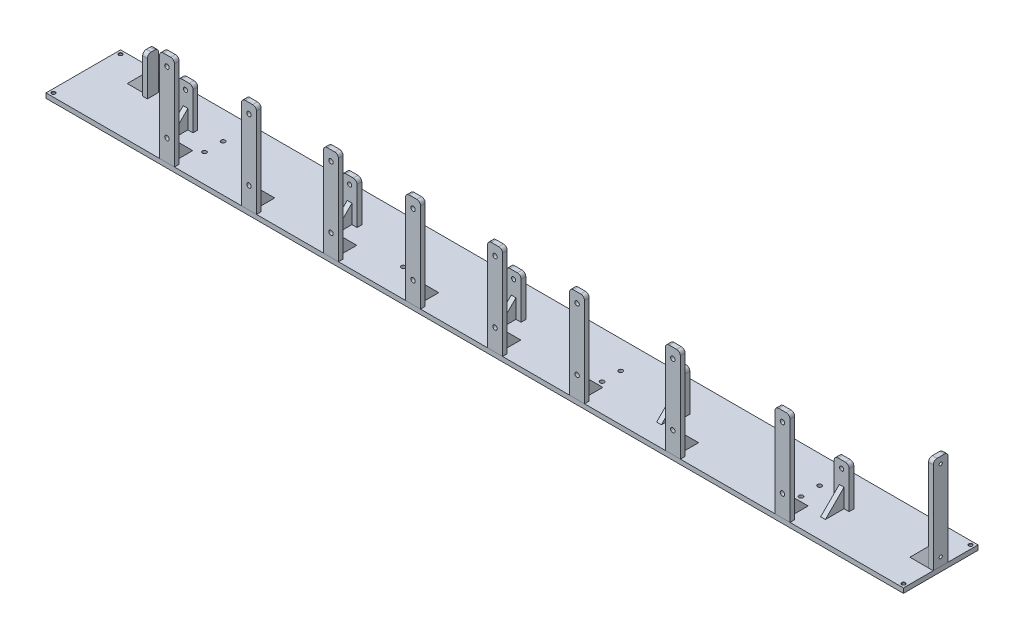
SolidWorks part; units mm, degrees
material "AISI 304"
ref_plane "Plan de face" through (0, 0, 0) normal (0, 0, 1) x (1, 0, 0)
ref_plane "Plan de dessus" through (0, 0, 0) normal (0, 1, 0) x (1, 0, 0)
ref_plane "Plan de droite" through (0, 0, 0) normal (1, 0, 0) x (0, 0, -1)
sketch "Esquisse1" plane through (0, 0, 0) normal (0, 1, 0) x (1, 0, 0)
  line L1 (-575, -50) -> (575, -50)
  line L2 (-575, -50) -> (-575, 50)
  line L3 (-575, 50) -> (575, 50)
  line L4 (575, -50) -> (575, 50)
  line L5 (-575, -50) -> (575, 50) construction
  line L6 (-575, 50) -> (575, -50) construction
  point P0 (0, 0)
  dimension "D1" = 1150
  dimension "D2" = 100
extrude "Boss.-Extru.1" add sketch "Esquisse1" along normal blind 6.35
hole_wizard "Dégagement M52" positions "Esquisse9" profile "Esquisse11" hole size "M5" standard "Ansi Metric" end condition up to next
sketch "Esquisse9" plane through (0, 6.35, 0) normal (0, 1, 0) x (1, 0, 0)
  line L2 (-400, 50) -> (-400, -50) construction
  line L3 (575, 50) -> (-575, 50) construction
  line L4 (-575, -50) -> (575, -50) construction
  line L6 (-133.3333, -50) -> (-133.3333, 50) construction
  line L8 (133.3333, 50) -> (133.3333, -50) construction
  line L10 (400, -50) -> (400, 50) construction
  line L12 (-400, 0) -> (-133.3333, 0) construction
  line L13 (-133.3333, 0) -> (133.3333, 0) construction
  line L14 (133.3333, 0) -> (400, 0) construction
  line L16 (-400, 12.5) -> (400, 12.5) construction
  line L18 (400, -12.5) -> (-400, -12.5) construction
  point P35 (-400, 12.5)
  point P36 (400, 12.5)
  point P39 (400, -12.5)
  point P40 (-400, -12.5)
  point P47 (-133.3333, -12.5)
  point P49 (-133.3333, 12.5)
  point P51 (133.3333, 12.5)
  point P53 (133.3333, -12.5)
  dimension "D1" = 25
  dimension "D3" = 800
sketch "Esquisse11" plane through (133.3333, 6.35, 12.5) normal (1, 0, 0) x (0, 0, 1)
  line L0 (0, 0) -> (0, 6.35)
  line L1 (0, 6.35) -> (2.75, 6.35)
  line L2 (2.75, 6.35) -> (2.75, 0)
  line L5 (2.75, 0) -> (0, 0)
  line L11 (0, -6.35) -> (0, 107.95) construction
  dimension "Diamètre du perçage jusqu'au prochain" = 5.5
  dimension "Profondeur du perçage jusqu'au prochain" = 6.35
ref_plane "Plan3" through (-500, 0, 0) normal (-1, 0, 0) x (0, 0, 1)
sketch "Esquisse5" plane through (-500, 0, 0) normal (-1, 0, 0) x (0, 0, 1)
  line L0 (-50, 6.35) -> (50, 6.35) construction
  line L1 (-26, 6.35) -> (-11, 6.35)
  line L2 (-26, 6.35) -> (-26, 53.35)
  line L3 (-21, 58.35) -> (-16, 58.35)
  line L4 (-11, 6.35) -> (-11, 53.35)
  line L7 (-18.5, 99.85) -> (-18.5, 6.35) construction
  line L8 (-50, 6.35) -> (-50, 0) construction
  arc A0 (-16, 58.35) -> (-11, 53.35) centre (-16, 53.35) cw
  arc A1 (-26, 53.35) -> (-21, 58.35) centre (-21, 53.35) cw
  dimension "D2" = 5
  dimension "D1" = 15
  dimension "D3" = 31.5
  dimension "D4" = 52
extrude "Boss.-Extru.4" add sketch "Esquisse5" along normal blind 6.35 separate body
ref_plane "Plan4" through (0, 0, -18.5) normal (0, 0, 1) x (1, 0, 0)
sketch "Esquisse6" plane through (0, 0, -18.5) normal (0, 0, 1) x (1, 0, 0)
  line L0 (-506.35, 31.35) -> (-531.35, 6.35)
  line L1 (-506.35, 6.35) -> (-506.35, 53.35) construction
  line L2 (-575, 6.35) -> (575, 6.35) construction
  line L3 (-531.35, 6.35) -> (-506.35, 6.35)
  line L4 (-506.35, 6.35) -> (-506.35, 31.35)
  dimension "D1" = 45
  dimension "D2" = 25
extrude "Boss.-Extru.5" add sketch "Esquisse6" along normal mid plane 6.35 separate body
ref_plane "Plan1" through (0, 0, -8.5) normal (0, 0, -1) x (-1, 0, 0)
sketch "Esquisse2" plane through (0, 0, -8.5) normal (0, 0, -1) x (-1, 0, 0)
  line L0 (-575, 6.35) -> (575, 6.35) construction
  line L1 (450, 6.35) -> (430, 6.35)
  line L2 (450, 6.35) -> (450, 56.35)
  line L3 (445, 61.35) -> (435, 61.35)
  line L4 (430, 6.35) -> (430, 56.35)
  arc A0 (435, 61.35) -> (430, 56.35) centre (435, 56.35) ccw
  arc A1 (450, 56.35) -> (445, 61.35) centre (445, 56.35) ccw
  point P10 (440, 61.35)
  dimension "D1" = 5
  dimension "D2" = 55
  dimension "D3" = 20
  dimension "D4" = 440
extrude "Boss.-Extru.2" add sketch "Esquisse2" against normal blind 6.35 separate body
ref_plane "Plan2" through (-440, 0, 0) normal (1, 0, 0) x (0, 0, -1)
sketch "Esquisse4" plane through (-440, 0, 0) normal (1, 0, 0) x (0, 0, -1)
  line L0 (2.15, 31.35) -> (-22.85, 6.35)
  line L1 (2.15, 56.35) -> (2.15, 6.35) construction
  line L2 (-50, 6.35) -> (50, 6.35) construction
  line L3 (2.15, 31.35) -> (2.15, 6.35)
  line L4 (2.15, 6.35) -> (-22.85, 6.35)
  dimension "D1" = 45
  dimension "D2" = 25
extrude "Boss.-Extru.3" add sketch "Esquisse4" along normal mid plane 6.35 separate body
hole_wizard "Dégagement M51" positions "Esquisse7" profile "Esquisse8" hole size "M5" standard "Ansi Metric" end condition through all
sketch "Esquisse7" plane through (0, 0, -2.15) normal (0, 0, 1) x (1, 0, 0)
  line L0 (-440, 61.35) -> (-440, 51.35) construction
  line L1 (-445, 61.35) -> (-435, 61.35) construction
  line L2 (-440, -3.4925) -> (-440, 3.4925) construction
  point P0 (-440, 51.35)
  dimension "D1" = 10
sketch "Esquisse8" plane through (-440, 51.35, -2.15) normal (1, 0, 0) x (0, -1, 0)
  line L0 (0, 0) -> (0, 47.85)
  line L1 (0, 47.85) -> (2.75, 47.85)
  line L2 (2.75, 47.85) -> (2.75, 0.025)
  line L3 (2.75, 0.025) -> (2.775, 0)
  line L5 (2.775, 0) -> (0, 0)
  line L6 (-2.75, 0.025) -> (-2.775, 0) construction
  line L11 (0, -6.35) -> (0, 107.95) construction
  dimension "Diamètre du perçage jusqu'au prochain" = 5.5
  dimension "Profondeur du perçage jusqu'au prochain" = 47.85
  dimension "Diamètre du fraisage entrant" = 5.55
  dimension "Angle du fraisage entrant" = 90
pattern_linear "Répétition linéaire1" count 5 spacing 220 along (1, 0, 0) of "Boss.-Extru.2", "Boss.-Extru.3", "Dégagement M51"
sketch "Esquisse12" plane through (0, 0, 50) normal (0, 0, 1) x (1, 0, 0)
  line L0 (-575, 6.35) -> (575, 6.35) construction
  line L1 (-422.75, 6.35) -> (-402.75, 6.35)
  line L2 (-422.75, 6.35) -> (-422.75, 126.35)
  line L3 (-417.75, 131.35) -> (-407.75, 131.35)
  line L4 (-402.75, 6.35) -> (-402.75, 126.35)
  line L5 (-312.75, 6.35) -> (-292.75, 6.35)
  line L6 (-312.75, 6.35) -> (-312.75, 126.35)
  line L7 (-307.75, 131.35) -> (-297.75, 131.35)
  line L8 (-292.75, 6.35) -> (-292.75, 126.35)
  line L9 (-202.75, 6.35) -> (-182.75, 6.35)
  line L10 (-202.75, 6.35) -> (-202.75, 126.35)
  line L11 (-197.75, 131.35) -> (-187.75, 131.35)
  line L12 (-182.75, 6.35) -> (-182.75, 126.35)
  line L13 (-92.75, 6.35) -> (-72.75, 6.35)
  line L14 (-92.75, 6.35) -> (-92.75, 126.35)
  line L15 (-87.75, 131.35) -> (-77.75, 131.35)
  line L16 (-72.75, 6.35) -> (-72.75, 126.35)
  line L17 (17.25, 6.35) -> (37.25, 6.35)
  line L18 (17.25, 6.35) -> (17.25, 126.35)
  line L19 (22.25, 131.35) -> (32.25, 131.35)
  line L20 (37.25, 6.35) -> (37.25, 126.35)
  line L21 (127.25, 6.35) -> (147.25, 6.35)
  line L22 (127.25, 6.35) -> (127.25, 126.35)
  line L23 (132.25, 131.35) -> (142.25, 131.35)
  line L24 (147.25, 6.35) -> (147.25, 126.35)
  line L25 (255.75, 6.35) -> (275.75, 6.35)
  line L26 (255.75, 6.35) -> (255.75, 126.35)
  line L27 (260.75, 131.35) -> (270.75, 131.35)
  line L28 (275.75, 6.35) -> (275.75, 126.35)
  line L29 (402.75, 6.35) -> (422.75, 6.35)
  line L30 (402.75, 6.35) -> (402.75, 126.35)
  line L31 (407.75, 131.35) -> (417.75, 131.35)
  line L32 (422.75, 6.35) -> (422.75, 126.35)
  arc A0 (-407.75, 131.35) -> (-402.75, 126.35) centre (-407.75, 126.35) cw
  arc A1 (-422.75, 126.35) -> (-417.75, 131.35) centre (-417.75, 126.35) cw
  arc A2 (-297.75, 131.35) -> (-292.75, 126.35) centre (-297.75, 126.35) cw
  arc A3 (-312.75, 126.35) -> (-307.75, 131.35) centre (-307.75, 126.35) cw
  arc A4 (-187.75, 131.35) -> (-182.75, 126.35) centre (-187.75, 126.35) cw
  arc A5 (-202.75, 126.35) -> (-197.75, 131.35) centre (-197.75, 126.35) cw
  arc A6 (-77.75, 131.35) -> (-72.75, 126.35) centre (-77.75, 126.35) cw
  arc A7 (-92.75, 126.35) -> (-87.75, 131.35) centre (-87.75, 126.35) cw
  arc A8 (32.25, 131.35) -> (37.25, 126.35) centre (32.25, 126.35) cw
  arc A9 (17.25, 126.35) -> (22.25, 131.35) centre (22.25, 126.35) cw
  arc A10 (142.25, 131.35) -> (147.25, 126.35) centre (142.25, 126.35) cw
  arc A11 (127.25, 126.35) -> (132.25, 131.35) centre (132.25, 126.35) cw
  arc A12 (270.75, 131.35) -> (275.75, 126.35) centre (270.75, 126.35) cw
  arc A13 (255.75, 126.35) -> (260.75, 131.35) centre (260.75, 126.35) cw
  arc A14 (417.75, 131.35) -> (422.75, 126.35) centre (417.75, 126.35) cw
  arc A15 (402.75, 126.35) -> (407.75, 131.35) centre (407.75, 126.35) cw
  dimension "D1" = 5
  dimension "D5" = 110
  dimension "D6" = 128.5
  dimension "D7" = 147
  dimension "D8" = 20
  dimension "D9" = 125
  dimension "D10" = 422.75
  dimension "D2" = 6
  dimension "D3" = 2
  dimension "D4" = 2
extrude "Boss.-Extru.6" add sketch "Esquisse12" against normal blind 6.35 separate body
ref_plane "Plan5" through (-412.75, 0, 0) normal (-1, 0, 0) x (0, 0, 1)
sketch "Esquisse14" plane through (-412.75, 0, 0) normal (-1, 0, 0) x (0, 0, 1)
  line L0 (43.65, 31.35) -> (43.65, 6.35)
  line L1 (43.65, 126.35) -> (43.65, 6.35) construction
  line L2 (43.65, 6.35) -> (18.65, 6.35)
  line L3 (-50, 6.35) -> (50, 6.35) construction
  line L4 (18.65, 6.35) -> (43.65, 31.35)
  dimension "D1" = 45
  dimension "D2" = 25
extrude "Boss.-Extru.7" add sketch "Esquisse14" along normal mid plane 6.35 separate body
pattern_linear "Répétition linéaire2" count 6 spacing 110 along (1, 0, 0) of bodies 125
pattern_linear "Répétition linéaire3" count 2 spacing 128.5 along (1, 0, 0) of bodies 130
pattern_linear "Répétition linéaire4" count 2 spacing 147 along (1, 0, 0) of bodies 131
hole_wizard "Trou pour taraudage pour trou taraudé M7x1.01" positions "Esquisse17" profile "Esquisse18" hole size "M7x1.0" standard "Ansi Metric" end condition up to next
sketch "Esquisse17" plane through (0, 0, 50) normal (0, 0, 1) x (1, 0, 0)
  line L0 (-412.75, 6.35) -> (-412.75, 35) construction
  line L1 (-422.75, 6.35) -> (-402.75, 6.35) construction
  line L2 (-412.75, 35) -> (-412.75, 118) construction
  line L4 (-575, 0) -> (575, 0) construction
  point P0 (-412.75, 118)
  point P2 (-412.75, 35)
  point P19 (-302.75, 118)
  point P20 (-302.75, 35)
  point P21 (-192.75, 118)
  point P22 (-192.75, 35)
  point P23 (-82.75, 118)
  point P24 (-82.75, 35)
  point P25 (27.25, 118)
  point P26 (27.25, 35)
  point P27 (137.25, 118)
  point P28 (137.25, 35)
  point P34 (265.75, 118)
  point P35 (265.75, 35)
  point P41 (412.75, 118)
  point P42 (412.75, 35)
  dimension "D1" = 35
  dimension "D2" = 118
  dimension "D4" = 110
  dimension "D6" = 128.5
  dimension "D8" = 147
  dimension "D3" = 6
  dimension "D5" = 2
  dimension "D7" = 2
sketch "Esquisse18" plane through (-412.75, 118, 50) normal (1, 0, 0) x (0, -1, 0)
  line L0 (0, 0) -> (0, 6.351)
  line L1 (0, 6.351) -> (3, 6.351)
  line L2 (3, 6.351) -> (3, 0)
  line L5 (3, 0) -> (0, 0)
  line L11 (0, -6.35) -> (0, 107.95) construction
  dimension "Diamètre du perçage jusqu'au prochain" = 6
  dimension "Profondeur du perçage jusqu'au prochain" = 6.351
hole_wizard "Trou taraudé M5x0.81" positions "Esquisse15" profile "Esquisse16" tap size "M5x0.8" standard "Ansi Metric" end condition up to next
sketch "Esquisse15" plane through (0, 6.35, 0) normal (0, 1, 0) x (1, 0, 0)
  line L0 (575, -50) -> (575, 50) construction
  line L1 (-575, -50) -> (575, -50) construction
  point P0 (570, -45)
  dimension "D1" = 5
  dimension "D2" = 5
sketch "Esquisse16" plane through (570, 6.35, 45) normal (1, 0, 0) x (0, 0, 1)
  line L0 (0, 0) -> (0, 6.351)
  line L1 (0, 6.351) -> (2.1, 6.351)
  line L2 (2.1, 6.351) -> (2.1, 0.425)
  line L3 (2.1, 0.425) -> (2.525, 0)
  line L5 (2.525, 0) -> (0, 0)
  line L6 (-2.1, 0.425) -> (-2.525, 0) construction
  line L11 (0, -6.35) -> (0, 107.95) construction
  dimension "Diamètre du trou pour taraudage jusqu'au prochain" = 4.2
  dimension "Profondeur du trou pour taraudage jusqu'au prochain" = 6.351
  dimension "Diamètre du fraisage entrant" = 5.05
  dimension "Angle du fraisage entrant" = 90
cosmetic thread "Filetage de perçage1" parameters "D2"=5
mirror "Symétrie1" about plane through (0, 0, 0) normal (0, 0, 1) of "Trou taraudé M5x0.81"
cosmetic thread "Filetage de perçage2" parameters "D2"=5
mirror "Symétrie2" about plane through (0, 0, 0) normal (1, 0, 0) of "Trou taraudé M5x0.81", "Symétrie1"
cosmetic thread "Filetage de perçage3" parameters "D2"=5
cosmetic thread "Filetage de perçage4" parameters "D2"=5
sketch "Esquisse19" plane through (575, 0, 0) normal (1, 0, 0) x (0, 0, -1)
  line L0 (-10, 6.35) -> (10, 6.35)
  line L1 (-22.85, 6.35) -> (2.15, 6.35) construction
  line L2 (-50, 6.35) -> (50, 6.35) construction
  line L3 (10, 6.35) -> (10, 129.35)
  line L4 (5, 134.35) -> (-5, 134.35)
  line L5 (-10, 129.35) -> (-10, 6.35)
  line L6 (0, 0) -> (0, 6.35) construction
  arc A0 (10, 129.35) -> (5, 134.35) centre (5, 129.35) ccw
  arc A1 (-5, 134.35) -> (-10, 129.35) centre (-5, 129.35) ccw
  dimension "D2" = 5
  dimension "D1" = 20
  dimension "D3" = 128
extrude "Boss.-Extru.8" add sketch "Esquisse19" against normal blind 6.35 separate body
ref_plane "Plan6" through (0, 0, 0) normal (0, 0, 1) x (1, 0, 0)
sketch "Esquisse20" plane through (0, 0, 0) normal (0, 0, 1) x (1, 0, 0)
  line L0 (568.65, 31.35) -> (543.65, 6.35)
  line L1 (568.65, 129.35) -> (568.65, 6.35) construction
  line L2 (-575, 6.35) -> (575, 6.35) construction
  line L3 (543.65, 6.35) -> (568.65, 6.35)
  line L4 (568.65, 6.35) -> (568.65, 31.35)
  dimension "D1" = 45
  dimension "D2" = 25
extrude "Boss.-Extru.9" add sketch "Esquisse20" against normal blind 6.35 from surface separate body starting at face at (571.825, 67.85, 10)
extrude "Boss.-Extru.10" add sketch "Esquisse20<2>" along normal blind 6.35 from surface separate body starting at face at (571.825, 67.85, -10)
sketch "Esquisse20<2>" plane through (0, 0, 0) normal (0, 0, 1) x (1, 0, 0) same geometry as "Esquisse20"
hole_wizard "Trou taraudé M5x0.82" positions "Esquisse21" profile "Esquisse22" tap size "M5x0.8" standard "Ansi Metric" end condition up to next
sketch "Esquisse21" plane through (575, 0, 0) normal (1, 0, 0) x (0, 0, -1)
  line L0 (0, 125.35) -> (0, 17.35) construction
  line L2 (-50, 6.35) -> (50, 6.35) construction
  line L3 (0, 6.35) -> (0, 17.35) construction
  point P0 (0, 17.35)
  point P2 (0, 125.35)
  point P9 (0, 71.35)
  dimension "D1" = 108
  dimension "D2" = 65
sketch "Esquisse22" plane through (575, 17.35, 0) normal (0, 1, 0) x (0, 0, -1)
  line L0 (0, 0) -> (0, 1018.175)
  line L1 (0, 1018.175) -> (2.1, 1018.175)
  line L2 (2.1, 1018.175) -> (2.1, 0)
  line L5 (2.1, 0) -> (0, 0)
  line L11 (0, -6.35) -> (0, 107.95) construction
  dimension "Diamètre du trou pour taraudage jusqu'au prochain" = 4.2
  dimension "Profondeur du trou pour taraudage jusqu'au prochain" = 1018.175
cosmetic thread "Filetage de perçage5" parameters "D2"=5
cosmetic thread "Filetage de perçage6" parameters "D2"=5
